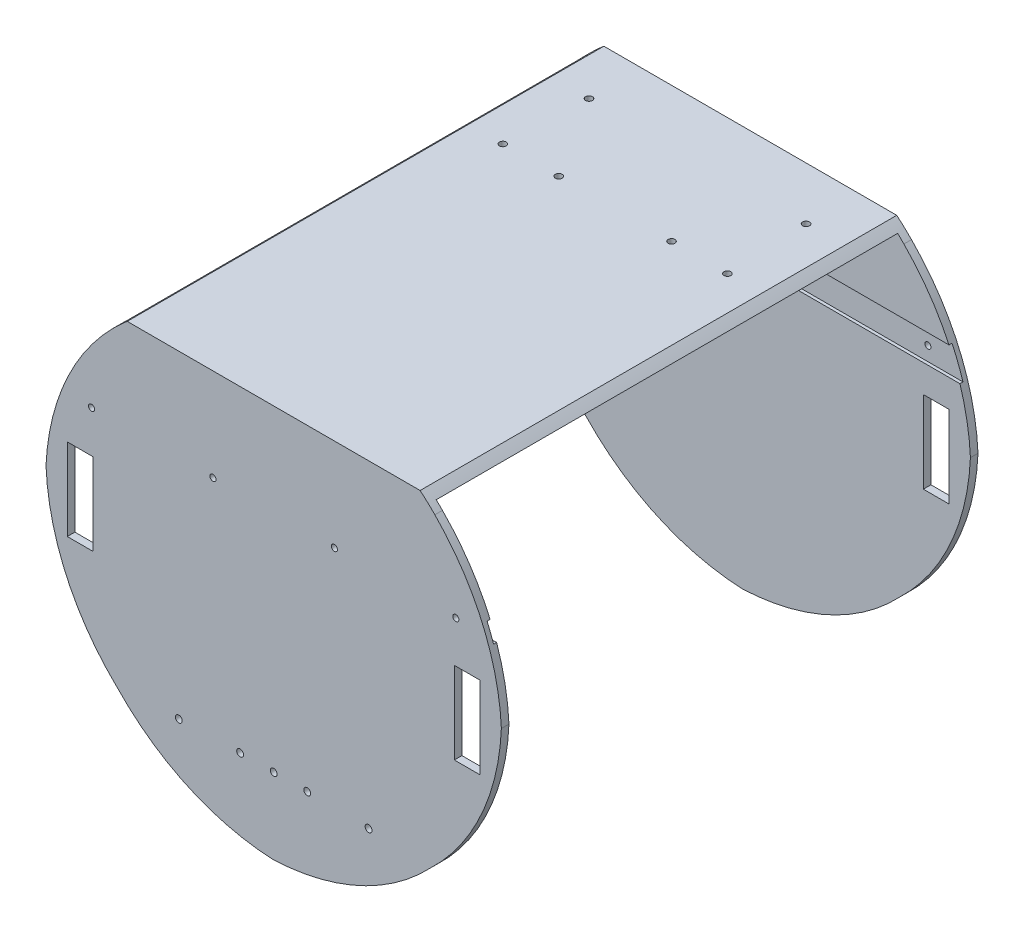
SolidWorks part; units mm, degrees
material "ABS"
ref_plane "Front Plane" through (0, 0, 0) normal (0, 0, 1) x (1, 0, 0)
ref_plane "Top Plane" through (0, 0, 0) normal (0, 1, 0) x (1, 0, 0)
ref_plane "Right Plane" through (0, 0, 0) normal (1, 0, 0) x (0, 0, -1)
sketch "Sketch1" plane through (0, 0, 0) normal (1, 0, 0) x (0, 0, -1)
  line L0 (-152, 0) -> (152, 0) construction
  line L1 (-152, 0) -> (-152, 254)
  line L2 (-152, 254) -> (152, 254)
  line L3 (152, 254) -> (152, 0)
  line L5 (-157, 0) -> (-157, 259)
  line L6 (-157, 259) -> (157, 259)
  line L7 (157, 259) -> (157, 0)
  line L8 (157, 0) -> (152, 0)
  line L10 (-152, 0) -> (-157, 0)
  point P4 (0, 0)
  dimension "D1" = 304
  dimension "D2" = 5
  dimension "D3" = 5
  dimension "D4" = 5
  dimension "D7" = 254
extrude "Boss-Extrude1" add sketch "Sketch1" along normal blind 150 and the other way blind 150
sketch "Sketch2" plane through (0, 0, 0) normal (0, 0, 1) x (1, 0, 0)
  line L1 (0, 150) -> (0, 0) construction
  line L2 (0, 150) -> (150, 150) construction
  line L3 (0, 150) -> (103.1245, 46.8755) construction
  line L4 (0, 150) -> (56.5109, 13.5707) construction
  line L5 (0, 150) -> (136.4293, 93.4891) construction
  line L6 (56.5109, 13.5707) -> (0, 13.5707) construction
  line L7 (136.4293, 93.4891) -> (136.4293, 150) construction
  line L8 (0, 150) -> (131.304, 216.3149) construction
  line L9 (0, 150) -> (0, 295.5) construction
  line L10 (0, 150) -> (106.1806, 249.9895) construction
  arc A0 (0, 0) -> (103.1245, 46.8755) centre (-6.3266, 150.7909) ccw
  arc A1 (150, 150) -> (103.1245, 46.8755) centre (-0.7909, 156.3266) cw
  arc A2 (106.1806, 249.9895) -> (150, 150) centre (-2.2818, 142.8605) cw
  arc A3 (106.1806, 249.9895) -> (0, 295.5) centre (-2.7988, 142.3499) ccw
  arc A4 (0, 0) -> (-103.1245, 46.8755) centre (6.3266, 150.7909) cw
  arc A5 (-150, 150) -> (-103.1245, 46.8755) centre (0.7909, 156.3266) ccw
  arc A6 (-106.1806, 249.9895) -> (-150, 150) centre (2.2818, 142.8605) ccw
  arc A7 (-106.1806, 249.9895) -> (0, 295.5) centre (2.7988, 142.3499) cw
  dimension "D1" = 150
  dimension "D2" = 22.5
  dimension "D3" = 22.5
  dimension "D4" = 145.84
  dimension "D5" = 147.67
  dimension "D6" = 147.1
  dimension "D7" = 26.796
  dimension "D8" = 145.5
  dimension "D9" = 43.28
  dimension "D10" = 145.85
extrude "Cut-Extrude1" cut sketch "Sketch2" against normal through all both and the other way through all flip side to cut contours A7 A6 A5 A4 A0 A1 A2 A3
sketch "Sketch3" plane through (0, 0, 0) normal (1, 0, 0) x (0, 0, -1)
  line L0 (-152, 198) -> (152, 198) construction
  line L1 (-154, 192.5) -> (-150, 192.5)
  line L2 (-154, 192.5) -> (-154, 203.5)
  line L3 (-154, 203.5) -> (-150, 203.5)
  line L4 (-150, 192.5) -> (-150, 203.5)
  line L5 (-154, 192.5) -> (-150, 203.5) construction
  line L6 (-154, 203.5) -> (-150, 192.5) construction
  line L7 (150, 188.75) -> (154, 188.75)
  line L8 (150, 188.75) -> (150, 207.25)
  line L9 (150, 207.25) -> (154, 207.25)
  line L10 (154, 188.75) -> (154, 207.25)
  line L11 (150, 188.75) -> (154, 207.25) construction
  line L12 (150, 207.25) -> (154, 188.75) construction
  line L13 (0, 0) -> (0, 198) construction
  point P0 (-152, 198)
  point P5 (152, 198)
  dimension "D1" = 304
  dimension "D2" = 4
  dimension "D3" = 198
  dimension "D4" = 11
extrude "Cut-Extrude2" cut sketch "Sketch3" against normal through all both and the other way through all
sketch "Sketch4" plane through (0, 0, 0) normal (0, 0, 1) x (1, 0, 0)
  line L0 (0, 0) -> (0, 259) construction
  line L1 (-96.4763, 259) -> (96.4763, 259) construction
  line L2 (-120, 198) -> (120, 198) construction
  circle A0 centre (-120, 198) radius 2
  circle A1 centre (120, 198) radius 2
  circle A2 centre (40, 198) radius 2
  circle A3 centre (-40, 198) radius 2
  point P8 (0, 198)
  dimension "D3" = 4
  dimension "D1" = 240
  dimension "D2" = 80
  dimension "D4" = 198
extrude "Cut-Extrude3" cut sketch "Sketch4" against normal through all both and the other way through all
sketch "Sketch6" plane through (0, 0, 0) normal (0, 0, 1) x (1, 0, 0)
  line L0 (-127.5, 143.5) -> (127.5, 143.5) construction
  line L1 (-136, 116.5) -> (-119, 116.5)
  line L2 (-136, 116.5) -> (-136, 170.5)
  line L3 (-136, 170.5) -> (-119, 170.5)
  line L4 (-119, 116.5) -> (-119, 170.5)
  line L5 (-136, 116.5) -> (-119, 170.5) construction
  line L6 (-136, 170.5) -> (-119, 116.5) construction
  line L7 (119, 170.5) -> (136, 170.5)
  line L8 (119, 170.5) -> (119, 116.5)
  line L9 (119, 116.5) -> (136, 116.5)
  line L10 (136, 170.5) -> (136, 116.5)
  line L11 (119, 170.5) -> (136, 116.5) construction
  line L12 (119, 116.5) -> (136, 170.5) construction
  line L13 (0, 143.5) -> (0, 0) construction
  point P0 (-127.5, 143.5)
  point P5 (127.5, 143.5)
  point P15 (127.5, 116.5)
  dimension "D1" = 272
  dimension "D2" = 17
  dimension "D3" = 54
  dimension "D4" = 116.5
extrude "Cut-Extrude4" cut sketch "Sketch6" against normal through all both and the other way through all
sketch "Sketch7" plane through (0, 0, 157) normal (0, 0, 1) x (1, 0, 0)
  line L0 (-22.11, 50) -> (22.11, 50) construction
  line L1 (62.5, 49.15) -> (-62.5, 49.15) construction
  line L2 (0, 50) -> (0, 49.15) construction
  line L3 (0, 0) -> (0, 49.15) construction
  circle A0 centre (0, 50) radius 2.25
  circle A1 centre (22.11, 50) radius 2.25
  circle A2 centre (-22.11, 50) radius 2.25
  circle A3 centre (-62.5, 49.15) radius 2.25
  circle A4 centre (62.5, 49.15) radius 2.25
  point P13 (0, 50)
  point P17 (0, 49.15)
  dimension "D1" = 4.5
  dimension "D2" = 4.5
  dimension "D3" = 22.11
  dimension "D4" = 62.5
  dimension "D5" = 0.85
  dimension "D6" = 100
extrude "Cut-Extrude5" cut sketch "Sketch7" against normal up to next
sketch "Sketch8" plane through (0, 259, 0) normal (0, 1, 0) x (1, 0, 0)
  line L0 (0, 157) -> (0, 0) construction
  line L1 (-96.4763, 157) -> (96.4763, 157) construction
  line L2 (-73.95, 67.95) -> (73.95, 67.95) construction
  line L3 (-71.5, 122.23) -> (71.5, 122.23) construction
  circle A2 centre (-73.95, 67.95) radius 2.25
  circle A3 centre (73.95, 67.95) radius 2.25
  circle A4 centre (37.15, 67.95) radius 2.25
  circle A5 centre (-37.15, 67.95) radius 2.25
  circle A6 centre (-71.5, 122.23) radius 2.25
  circle A7 centre (71.5, 122.23) radius 2.25
  point P8 (0, 67.95)
  point P17 (0, 122.23)
  dimension "D2" = 4.5
  dimension "D3" = 147.9
  dimension "D1" = 89.05
  dimension "D4" = 74.3
  dimension "D5" = 143
  dimension "D6" = 54.28
extrude "Cut-Extrude6" cut sketch "Sketch8" against normal up to next
fillet "Fillet1" radius 1 6 edges at (-71.5, 254, -124.48) (-73.95, 254, -70.2) (-37.15, 254, -70.2) (37.15, 254, -70.2) (73.95, 254, -70.2) (71.5, 254, -124.48)
